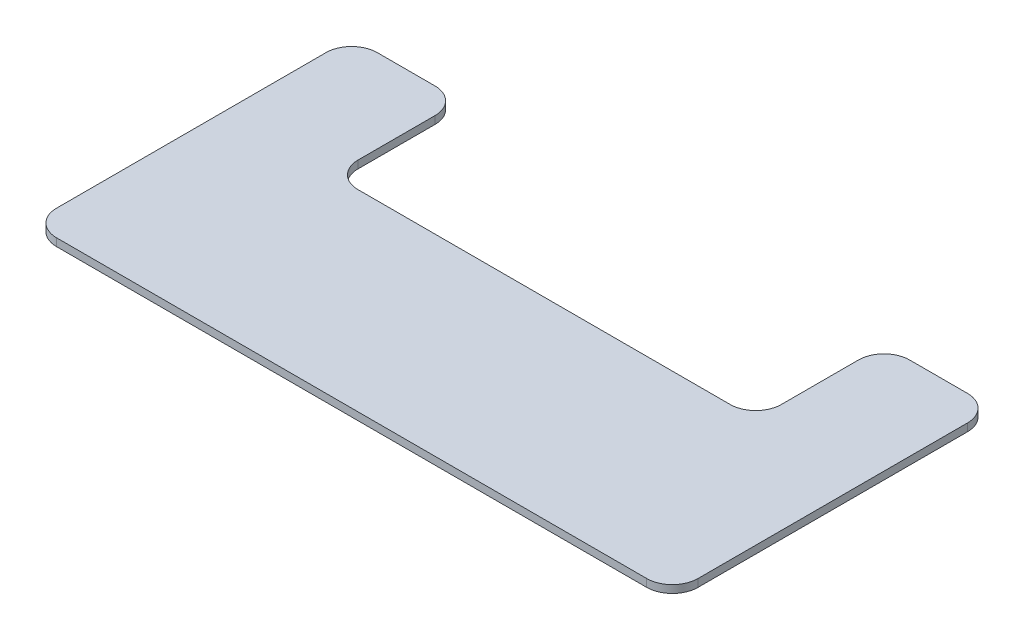
SolidWorks part; units mm, degrees
ref_plane "Front" through (0, 0, 0) normal (0, 0, 1) x (1, 0, 0)
ref_plane "Top" through (0, 0, 0) normal (0, 1, 0) x (1, 0, 0)
ref_plane "Right" through (0, 0, 0) normal (1, 0, 0) x (0, 0, -1)
sketch "Sketch16" plane through (0, 0, 0) normal (0, 1, 0) x (1, 0, 0)
  line L0 (-50, 0) -> (-50, 75) construction
  line L1 (-50, 0) -> (50, 0)
  line L2 (0, 0) -> (0, 75) construction
  line L3 (-50, 75) -> (50, 75)
  line L4 (50, 0) -> (50, 75) construction
  line L5 (50, 0) -> (115, 0)
  line L7 (50, 75) -> (72.5, 75)
  line L8 (125, 10) -> (125, 75)
  line L10 (125, 75) -> (125, 115)
  line L11 (115, 125) -> (92.5, 125)
  line L12 (82.5, 85) -> (82.5, 115)
  line L13 (-50, 0) -> (-115, 0)
  line L14 (-125, 10) -> (-125, 75)
  line L15 (-125, 75) -> (-125, 115)
  line L16 (-115, 125) -> (-92.5, 125)
  line L17 (-82.5, 85) -> (-82.5, 115)
  line L18 (-50, 75) -> (-72.5, 75)
  arc A0 (-115, 0) -> (-125, 10) centre (-115, 10) cw
  arc A1 (-125, 115) -> (-115, 125) centre (-115, 115) cw
  arc A2 (-92.5, 125) -> (-82.5, 115) centre (-92.5, 115) cw
  arc A3 (-82.5, 85) -> (-72.5, 75) centre (-72.5, 85) ccw
  arc A4 (72.5, 75) -> (82.5, 85) centre (72.5, 85) ccw
  arc A5 (92.5, 125) -> (82.5, 115) centre (92.5, 115) ccw
  arc A6 (125, 115) -> (115, 125) centre (115, 115) ccw
  arc A7 (115, 0) -> (125, 10) centre (115, 10) ccw
  point P11 (82.5, 0)
  point P21 (-125, 0)
  point P24 (-125, 125)
  point P27 (-82.5, 125)
  point P30 (-82.5, 75)
  point P33 (82.5, 75)
  point P36 (82.5, 125)
  point P39 (125, 125)
  point P42 (125, 0)
  dimension "D5" = 10
  dimension "D1" = 75
  dimension "D2" = 50
  dimension "D3" = 75
  dimension "D4" = 50
base flange "Base-Flange1" sketch "Sketch16" thickness 3 reverse thickness direction no parameters "D1"=1
sketch "Sketch22" plane through (0, 0, 0) normal (0, 1, 0) x (1, 0, 0)
  line L2 (50, 75) -> (50, 0)
  line L3 (-50, 75) -> (-50, 0)
sketch "Bend-Lines5" plane through (0, 0, 0) normal (0, 1, 0) x (1, 0, 0)
sketch "Bounding-Box5" plane through (0, 0, 0) normal (0, 1, 0) x (1, 0, 0)
sheet metal parameters "Sheet-Metal4" thickness 3 parameters "D1"=1
flat pattern "Flat-Pattern4"
sketch "Bend-Lines6" plane through (0, 0, 0) normal (0, 1, 0) x (1, 0, 0)
  point P0 (-50, 75)
  point P1 (-50, 0)
  point P2 (50, 0)
  point P3 (50, 75)
sketch3d "Bounding-Box6"
  line L0 (-197.5, -85, 0) -> (52.5, -85, 0) construction
  line L1 (-197.5, 40, 0) -> (52.5, 40, 0) construction
  line L2 (-197.5, -85, 0) -> (-197.5, 40, 0) construction
  line L3 (52.5, -85, 0) -> (52.5, 40, 0) construction
